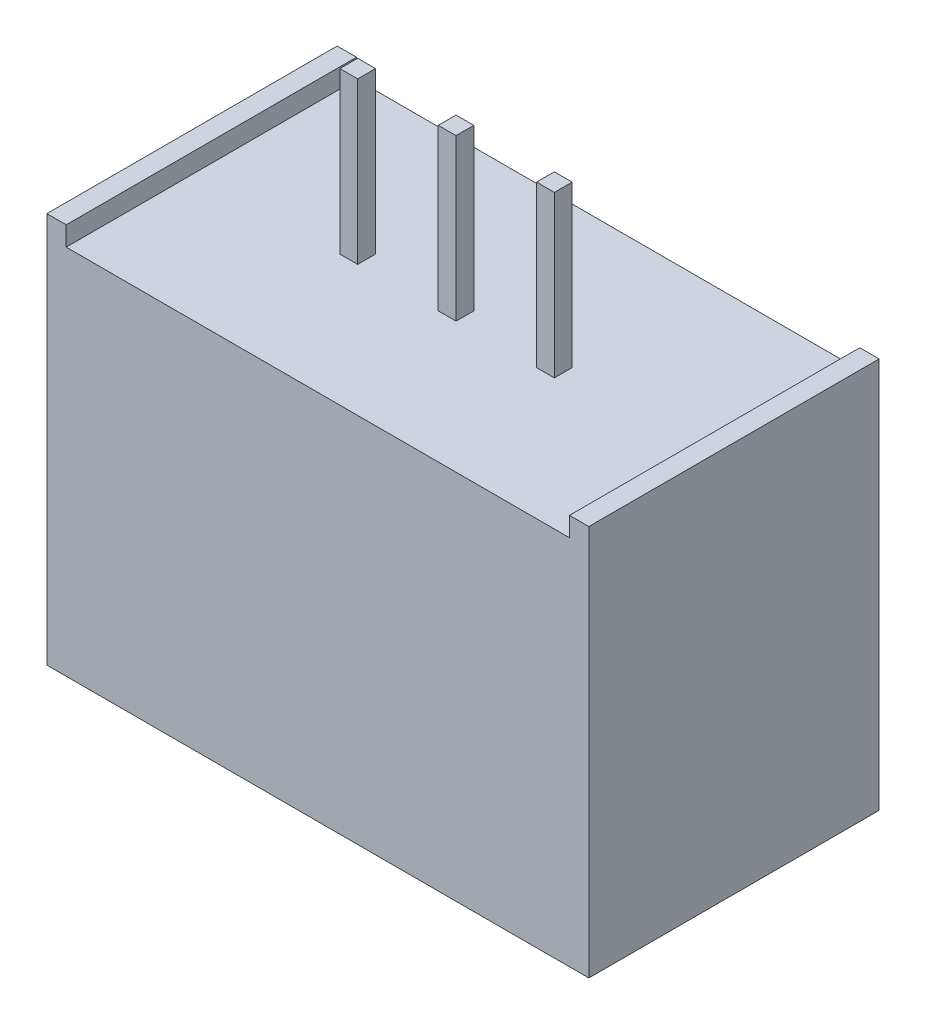
SolidWorks part; units mm, degrees
note: The reader was unsure of these and kept them because the rebuilt part matched: shared geometry of "Bottom View<3>", "Bottom View<4>".
ref_plane "Front Plane" through (0, 0, 0) normal (0, 0, 1) x (1, 0, 0)
ref_plane "Top Plane" through (0, 0, 0) normal (0, 1, 0) x (1, 0, 0)
ref_plane "Right Plane" through (0, 0, 0) normal (1, 0, 0) x (0, 0, -1)
sketch "Bottom View" plane through (0, 0, 0) normal (0, 1, 0) x (1, 0, 0)
  line L0 (0, 0) -> (0, 3.89) construction
  line L1 (0, 0) -> (2.54, 0) construction
  line L2 (2.54, 0) -> (5.08, 0) construction
  line L3 (-3.92, 3.89) -> (-3.92, -3.61)
  line L4 (5.08, 0) -> (9.58, 0) construction
  line L5 (9.58, -3.61) -> (9.58, 3.89)
  line L6 (9.58, 3.89) -> (-4.42, 3.89)
  line L7 (-4.42, 3.89) -> (-4.42, -3.61)
  line L8 (-4.42, -3.61) -> (9.58, -3.61)
  line L9 (9.08, 3.89) -> (9.08, -3.61)
  line L10 (0.23, -0.23) -> (-0.23, -0.23)
  line L11 (0.23, -0.23) -> (0.23, 0.23)
  line L12 (0.23, 0.23) -> (-0.23, 0.23)
  line L13 (-0.23, -0.23) -> (-0.23, 0.23)
  line L14 (0.23, -0.23) -> (-0.23, 0.23) construction
  line L15 (0.23, 0.23) -> (-0.23, -0.23) construction
  line L16 (2.77, -0.23) -> (2.31, -0.23)
  line L17 (2.77, -0.23) -> (2.77, 0.23)
  line L18 (2.77, 0.23) -> (2.31, 0.23)
  line L19 (2.31, -0.23) -> (2.31, 0.23)
  line L20 (2.77, -0.23) -> (2.31, 0.23) construction
  line L21 (2.77, 0.23) -> (2.31, -0.23) construction
  line L22 (5.31, -0.23) -> (4.85, -0.23)
  line L23 (5.31, -0.23) -> (5.31, 0.23)
  line L24 (5.31, 0.23) -> (4.85, 0.23)
  line L25 (4.85, -0.23) -> (4.85, 0.23)
  line L26 (5.31, -0.23) -> (4.85, 0.23) construction
  line L27 (5.31, 0.23) -> (4.85, -0.23) construction
  line L28 (-0.23, -0.23) -> (-3.92, -0.23) construction
  text T0 "Bottom View" font "Century Gothic" height 0.5
  text T1 "1" font "Century Gothic" height 1
  dimension "D1" = 2.54
  dimension "D2" = 4.5
  dimension "D3" = 7.5
  dimension "D4" = 14
  dimension "D5" = 3.89
  dimension "D6" = 0.46
  dimension "D7" = 0.5
  dimension "D8" = 0.5
extrude "Boss-Extrude1" add sketch "Bottom View" against normal blind 10.1 contours L6 L7 L8 L5
extrude "Cut-Extrude1" cut sketch "Bottom View<3>" against normal blind 0.5 contours L9 L6 L3 L8 L10 L13 L12 L11 L16 L19 L18 L17 L22 L25 L24 L23 | L19 L16 L17 L18 | L25 L22 L23 L24
sketch "Bottom View<3>" plane through (0, 0, 0) normal (0, 1, 0) x (1, 0, 0) same geometry as "Bottom View"
extrude "Boss-Extrude2" add sketch "Bottom View<4>" along normal blind 4.15 from surface at -0.5 contours L13 L10 L11 L12 | L19 L16 L17 L18 | L25 L22 L23 L24 | L8 L5 L6 L7
sketch "Bottom View<4>" plane through (0, 0, 0) normal (0, 1, 0) x (1, 0, 0) same geometry as "Bottom View"
sketch "Sketch2" plane through (0, 0, -3.89) normal (0, 0, -1) x (-1, 0, 0)
  line L0 (4.42, -7.6) -> (-9.58, -7.6) construction
  line L1 (4.42, -10.1) -> (4.42, 0) construction
  line L2 (-9.58, -10.1) -> (-9.58, 0) construction
  line L3 (4.42, -5.1) -> (-9.58, -5.1) construction
  line L4 (4.42, -2.6) -> (-9.58, -2.6) construction
  line L5 (-9.58, -10.1) -> (4.42, -10.1) construction
  line L6 (0, -1.35) -> (0, 0) construction
  circle A0 centre (0, -1.35) radius 0.375
  text T0 "TRACO" font "Century Gothic" height 2
  text T1 "POWER" font "Century Gothic" height 2
  text T2 "TSR 2-2450" font "Century Gothic" height 1.5
  point P17 (0, 0)
  dimension "D5" = 0.75
  dimension "D1" = 2.5
  dimension "D2" = 2.5
  dimension "D3" = 2.5
  dimension "D4" = 1.25
split line "Split Line1"
